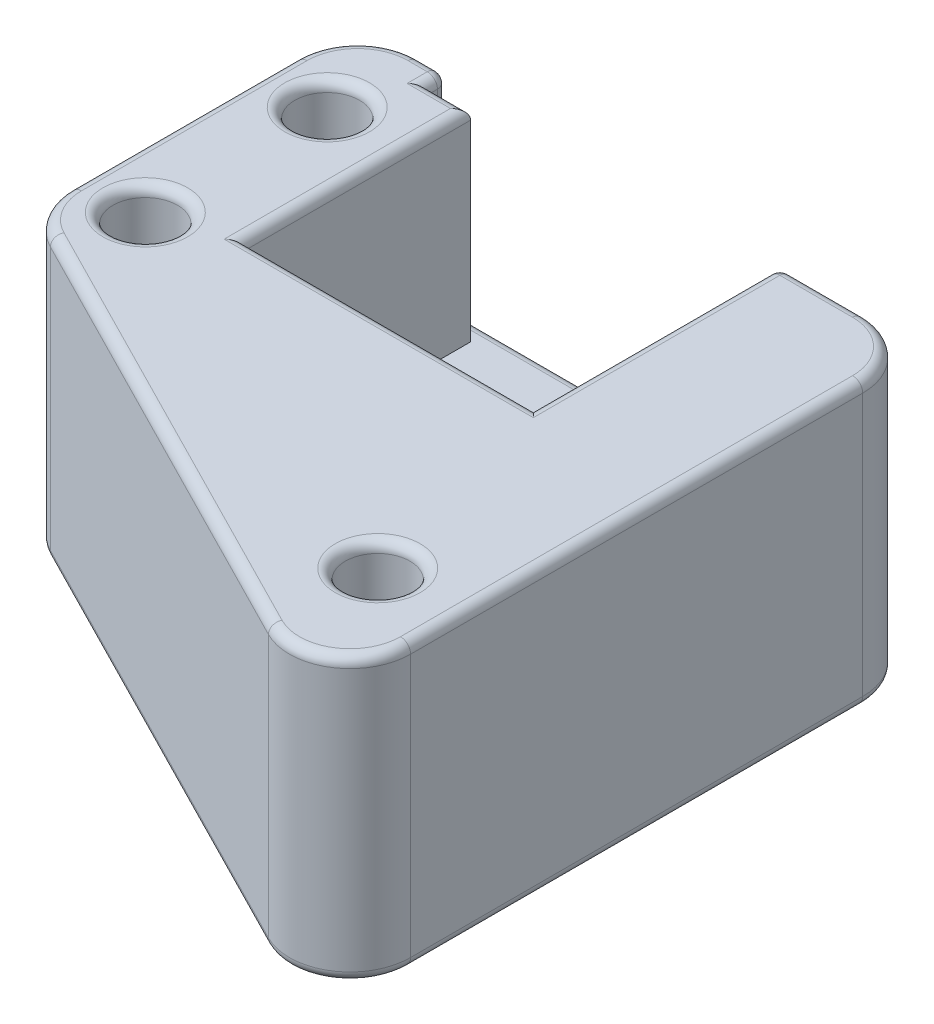
SolidWorks part; units mm, degrees
ref_plane "Front Plane" through (0, 0, 0) normal (0, 0, 1) x (1, 0, 0)
ref_plane "Top Plane" through (0, 0, 0) normal (0, 1, 0) x (1, 0, 0)
ref_plane "Right Plane" through (0, 0, 0) normal (1, 0, 0) x (0, 0, -1)
sketch "Sketch1" plane through (0, 0, 0) normal (0, 1, 0) x (1, 0, 0)
  line L0 (-3.25, 0) -> (3.25, 0) construction
  line L1 (6.4, 5) -> (-6.4, 5) construction
  line L2 (-14, -10) -> (14, -10)
  line L3 (-14, -10) -> (-14, 6)
  line L4 (-14, 6) -> (14, 6)
  line L5 (14, -10) -> (14, 6)
  line L6 (-11, -7.5) -> (10, -7.5) construction
  line L7 (0, 0) -> (0, -10) construction
  line L8 (-11, -7.5) -> (-11, 1.5) construction
  line L9 (-11, 1.5) -> (10, 1.5) construction
  line L10 (10, 1.5) -> (10, -7.5) construction
  circle A0 centre (3.25, 0) radius 0.85
  circle A1 centre (-3.25, 0) radius 0.85
  circle A2 centre (-11, -7.5) radius 1.6
  circle A3 centre (10, -7.5) radius 1.6 construction
  circle A4 centre (-11, -7.5) radius 3 construction
  circle A5 centre (-11, 1.5) radius 1.6
  circle A6 centre (10, 1.5) radius 1.6 construction
  circle A7 centre (-11, 1.5) radius 3 construction
  point P4 (0, 0)
  dimension "D1" = 1.7
  dimension "D2" = 6.5
  dimension "D6" = 3.2
  dimension "D8" = 6
  dimension "D9" = 9
  dimension "D10" = 2.5
  dimension "D3" = 16
  dimension "D4" = 28
  dimension "D5" = 1
  dimension "D7" = 21
  dimension "D11" = 4
extrude "Boss-Extrude1" add sketch "Sketch1" along normal blind 4
sketch "Sketch2" plane through (0, 4, 0) normal (0, 1, 0) x (1, 0, 0)
  line L0 (-9.5462, 6) -> (-9.5462, 5)
  line L1 (-7.4, -6.2) -> (6.9, -6.2)
  line L2 (6.9, -6.2) -> (6.9, 6)
  line L3 (-9.5462, 6) -> (-14, 6)
  line L4 (-14, 6) -> (-14, -10)
  line L5 (-14, -10) -> (14, -10)
  line L6 (14, -10) -> (14, 6)
  line L7 (14, 6) -> (6.9, 6)
  line L8 (14, -10) -> (14, 6) construction
  line L9 (14, 6) -> (-14, 6) construction
  line L10 (6.4, 1.3) -> (6.4, 5) construction
  line L11 (-14, 6) -> (-14, -10) construction
  line L13 (4.75, -1.2) -> (6.4, -1.2) construction
  line L14 (-9.5462, 5) -> (-7.4, 5)
  line L15 (-7.4, 5) -> (-7.4, -6.2)
  line L16 (-6.4, 5) -> (6.4, 5) construction
  line L17 (-6.4, 5) -> (-6.4, 1.3) construction
  circle A0 centre (-11, -7.5) radius 1.6 construction
  circle A1 centre (-11, -7.5) radius 1.6
  circle A5 centre (-11, 1.5) radius 1.6 construction
  circle A7 centre (-11, 1.5) radius 1.6
  dimension "D1" = 0.5
  dimension "D2" = 5
  dimension "D3" = 2
  dimension "D4" = 1
extrude "Boss-Extrude2" add sketch "Sketch2" along normal blind 10
sketch "Sketch4" plane through (0, 0, 0) normal (0, -1, 0) x (1, 0, 0)
  line L0 (14, 10) -> (14, 24.2667)
  line L1 (14, 24.2667) -> (-14, 10)
  line L2 (10, 17) -> (10, 7.5) construction
  line L3 (14, 10) -> (-14, 10)
  line L4 (-11, 7.5) -> (10, 7.5) construction
  circle A0 centre (10, 17) radius 1.6
  circle A2 centre (-11, 7.5) radius 1.6 construction
  dimension "D1" = 9.5
  dimension "D3" = 3.2
  dimension "D2" = 27
  dimension "D4" = 21
extrude "Boss-Extrude3" add sketch "Sketch4" against normal through all
fillet "Fillet2" radius 3 4 edges at (-14, 7, -6) (14, 7, -6) (-14, 7, 10) (14, 7, 24.2667)
fillet "Fillet1" radius 0.5 33 edges at (-3.25, 0, 0.85) (-14, 0, 2.5808) (14, 0, 8.1856) (3.25, 0, 0.85) (-11, 0, 9.1) (6.9, 9, -6) (-1.3231, 4, -6) (-9.5462, 9, -6) (0, 0, -6) (-9.5462, 14, -5.5) (-8.4731, 14, -5) (-7.4, 14, 0.6) (-0.25, 14, 6.2) (6.9, 14, 0.1) (8.95, 14, -6) (14, 14, 8.1856) (-14, 14, 2.5808) (-10.2731, 14, -6) (-11, 14, 9.1) (-11, 0, 0.1) (-11, 14, 0.1) (10, 0, 15.4) (-1.362, 0, 16.4394) (10, 14, 15.4) (-1.362, 14, 16.4394) (-13.5579, 0, 9.7291) (12.5675, 0, 21.9291) (13.1213, 0, -5.1213) (-13.1213, 0, -5.1213) (13.1213, 14, -5.1213) (12.5675, 14, 21.9291) (-13.5579, 14, 9.7291) (-13.1213, 14, -5.1213)
